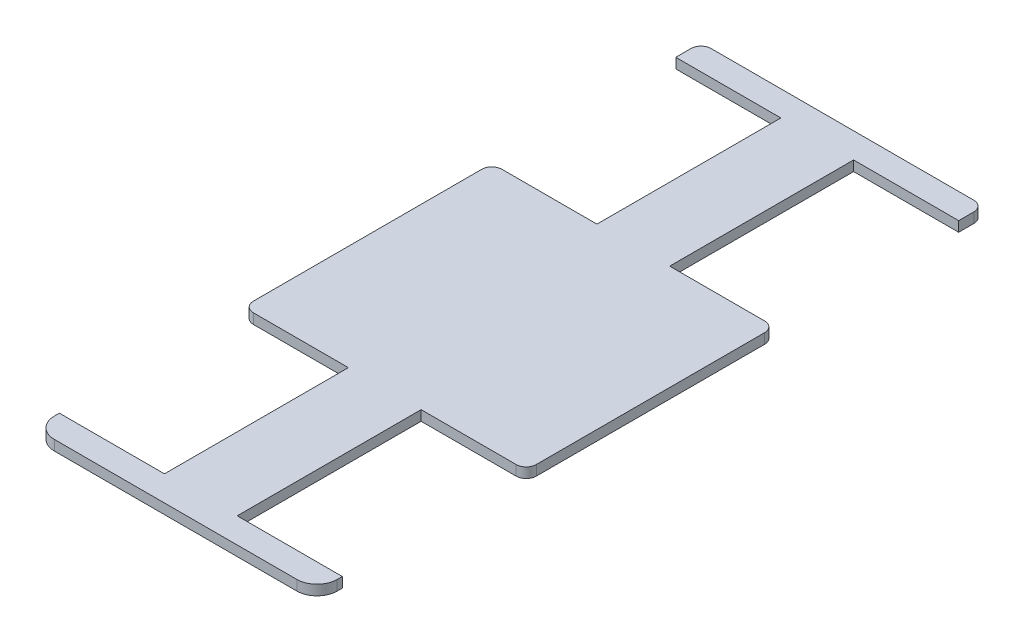
SolidWorks part; units mm, degrees
ref_plane "Front Plane" through (0, 0, 0) normal (0, 0, 1) x (1, 0, 0)
ref_plane "Top Plane" through (0, 0, 0) normal (0, 1, 0) x (1, 0, 0)
ref_plane "Right Plane" through (0, 0, 0) normal (1, 0, 0) x (0, 0, -1)
sketch "Sketch1" plane through (0, 0, 0) normal (0, 1, 0) x (1, 0, 0)
  line L0 (0, 0) -> (140, 0)
  line L1 (0, 0) -> (140, 0) construction
  line L2 (0, 0) -> (0, 330) construction
  line L3 (0, 330) -> (140, 330) construction
  line L4 (140, 0) -> (140, 330) construction
  line L5 (140, 0) -> (140, 12.5)
  line L6 (140, 12.5) -> (88, 12.5)
  line L7 (88, 12.5) -> (88, 103.5)
  line L8 (88, 103.5) -> (140, 103.5)
  line L9 (140, 103.5) -> (140, 226.5)
  line L10 (140, 226.5) -> (88, 226.5)
  line L11 (88, 226.5) -> (88, 317.5)
  line L12 (88, 317.5) -> (140, 317.5)
  line L13 (140, 317.5) -> (140, 330)
  line L14 (140, 330) -> (0, 330)
  line L15 (0, 330) -> (0, 317.5)
  line L16 (0, 317.5) -> (52, 317.5)
  line L17 (52, 317.5) -> (52, 226.5)
  line L18 (52, 226.5) -> (0, 226.5)
  line L19 (0, 226.5) -> (0, 103.5)
  line L20 (0, 103.5) -> (52, 103.5)
  line L21 (52, 103.5) -> (52, 12.5)
  line L22 (52, 12.5) -> (0, 12.5)
  line L23 (0, 12.5) -> (0, 0)
  dimension "D1" = 140
  dimension "D2" = 330
  dimension "D3" = 52
  dimension "D4" = 91
  dimension "D6" = 123
extrude "Boss-Extrude1" add sketch "Sketch1" along normal blind 5
fillet "Fillet1" radius 10 2 edges at (140, 2.5, 0) (0, 2.5, 0)
fillet "Fillet2" radius 5 6 edges at (0, 2.5, -330) (140, 2.5, -330) (140, 2.5, -226.5) (0, 2.5, -226.5) (140, 2.5, -103.5) (0, 2.5, -103.5)
